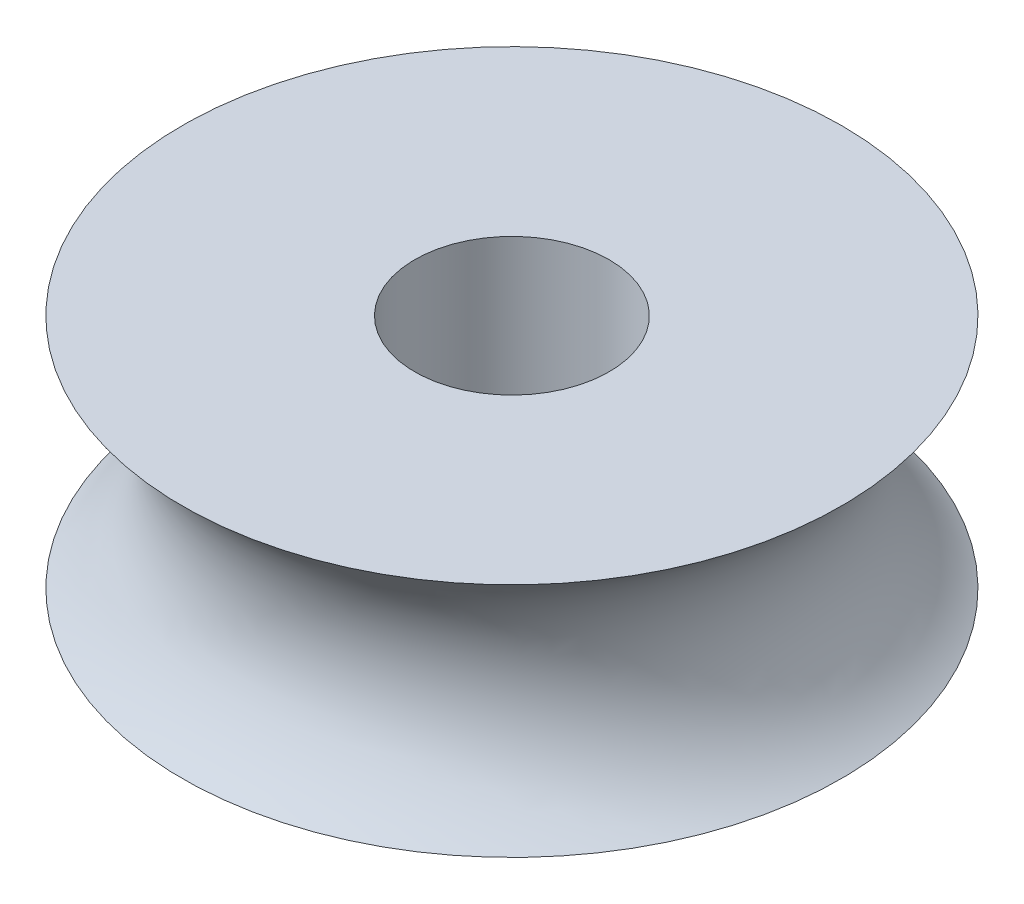
SolidWorks part; units mm, degrees
ref_plane "Plan de face" through (0, 0, 0) normal (0, 0, 1) x (1, 0, 0)
ref_plane "Plan de dessus" through (0, 0, 0) normal (0, 1, 0) x (1, 0, 0)
ref_plane "Plan de droite" through (0, 0, 0) normal (1, 0, 0) x (0, 0, -1)
sketch "Sketch1" plane through (0, 0, 0) normal (0, 0, 1) x (1, 0, 0)
  line L0 (3.5, 8.5) -> (3.5, 0)
  line L1 (3.5, 0) -> (11.8661, 0)
  line L2 (0, 0) -> (0, 8.5) construction
  line L3 (3.5, 8.5) -> (11.8661, 8.5)
  arc A1 (11.8661, 8.5) -> (11.8661, 0) centre (14.5, 4.25) ccw
  point P5 (0, 0)
  point P9 (0, 0)
  point P10 (0, 0)
  point P11 (0, 0)
  dimension "D3" = 5
  dimension "D1" = 8.5
  dimension "D2" = 14.5
  dimension "D4" = 3.5
  dimension "D5" = 8.3661
revolve "Revolve1" add sketch "Sketch1" angle 360 about L2
